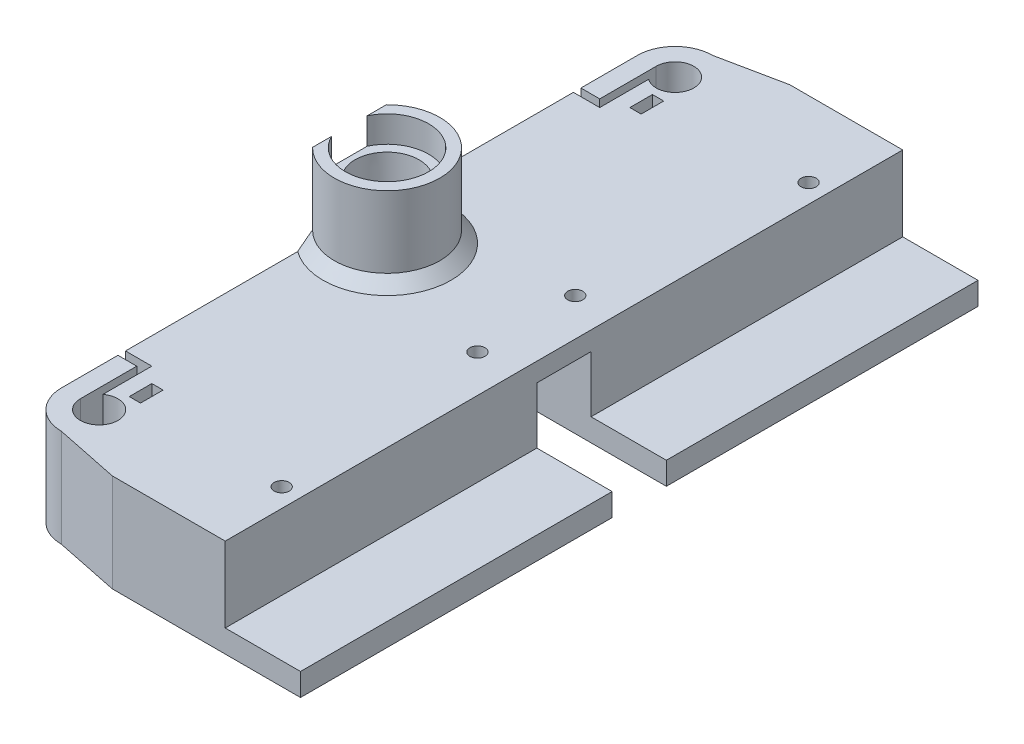
SolidWorks part; units mm, degrees
ref_plane "Płaszczyzna przednia" through (0, 0, 0) normal (0, 0, 1) x (1, 0, 0)
ref_plane "Płaszczyzna górna" through (0, 0, 0) normal (0, 1, 0) x (1, 0, 0)
ref_plane "Płaszczyzna prawa" through (0, 0, 0) normal (1, 0, 0) x (0, 0, -1)
sketch "Szkic1" plane through (0, 0, 0) normal (0, 0, 1) x (1, 0, 0)
  line L0 (10, -10) -> (10, -16)
  line L1 (10, -10) -> (-10, -10)
  line L2 (10, -10) -> (10, 10)
  line L3 (10, 10) -> (-10, 10)
  line L4 (-10, -10) -> (-10, 10)
  line L5 (10, -10) -> (-10, 10) construction
  line L6 (10, 10) -> (-10, -10) construction
  line L7 (10, -16) -> (-40, -16)
  line L8 (-40, -16) -> (-40, 10)
  line L9 (-40, 10) -> (-10, 10)
  point P0 (0, 0)
  dimension "D1" = 20
  dimension "D2" = 50
  dimension "D4" = 6
extrude "Dodanie-wyciągnięcie1" add sketch "Szkic1" along normal blind 180 contours L8 L7 L0 L1 L4 L3 region at (-21.6667, -4.3333, 0)
sketch "Szkic2" plane through (0, 10, 0) normal (0, 1, 0) x (1, 0, 0)
  line L0 (-10, -180) -> (-10, 0) construction
  line L3 (-40, -180) -> (-40, 0) construction
  line L4 (-40, 0) -> (-57, -3.5)
  line L5 (-40, -180) -> (-57, -176.5)
  line L6 (-67, -166.5) -> (-67, -13.5)
  line L7 (-40, 0) -> (-40, -180)
  circle A0 centre (-57, -13.5) radius 5
  circle A1 centre (-57, -166.5) radius 5
  circle A2 centre (-57, -13.5) radius 10
  circle A3 centre (-57, -166.5) radius 10
  circle A4 centre (-57, -90) radius 4
  point P14 (-40, -90)
  line M2 (-40, 0) -> (-40, -180)
  dimension "D1" = 47
  dimension "D2" = 10
  dimension "D6" = 8
  dimension "D3" = 153
  dimension "D4" = 76.5
  dimension "D5" = 5
extrude "Dodanie-wyciągnięcie2" add sketch "Szkic2" against normal blind 26 contours A2 A0 | A3 L5 L4 A2 L6 M2 | A3 A1 region at (-52.6707, 10, 90) region at (-50.1289, 10, 6.6289) region at (-63.8711, 10, 173.3711)
sketch "Szkic3" plane through (0, 10, 0) normal (0, 1, 0) x (1, 0, 0)
  line L0 (-62, -13.5) -> (-62, -28.5)
  line L1 (-62, -28.5) -> (-67, -28.5)
  line L2 (-67, -166.5) -> (-67, -13.5) construction
  line L3 (-67, -30.5) -> (-60, -30.5)
  line L4 (-60, -30.5) -> (-60, -17.5)
  line L5 (-67, -28.5) -> (-67, -30.5)
  circle A0 centre (-57, -13.5) radius 5 construction
  circle A1 centre (-57, -13.5) radius 5
  line M8 (-67, -13.5) -> (-67, -166.5)
  circle M13 centre (-57, -13.5) radius 5
  dimension "D3" = 10
  dimension "D1" = 2
  dimension "D2" = 2
  dimension "D4" = 15
extrude "Wytnij-wyciągnięcie1" cut sketch "Szkic3" against normal blind 26 contours L3 L4 L0 L1 M13 M8 region at (-61.9381, 10, 24.9644)
sketch "Szkic4" plane through (-67, 0, 0) normal (-1, 0, 0) x (0, 0, 1)
  line L0 (28.5, -16) -> (28.5, 10) construction
  line L1 (28.5, 10) -> (13.5, 10) construction
  circle A0 centre (23.5, 3) radius 1.75
  circle A1 centre (23.5, -9) radius 1.75
  dimension "D1" = 3.5
  dimension "D2" = 12
  dimension "D3" = 5
  dimension "D4" = 7
extrude "Wytnij-wyciągnięcie2" cut sketch "Szkic4" against normal blind 11
sketch "Szkic5" plane through (-67, 0, 0) normal (-1, 0, 0) x (0, 0, 1)
  line L0 (20.5, 4.7321) -> (20.5, 10)
  line L1 (23.5, 6.4641) -> (20.5, 4.7321)
  line L2 (20.5, 4.7321) -> (20.5, 1.2679)
  line L3 (20.5, 1.2679) -> (23.5, -0.4641)
  line L4 (23.5, -0.4641) -> (26.5, 1.2679)
  line L5 (26.5, 1.2679) -> (26.5, 4.7321)
  line L6 (26.5, 4.7321) -> (23.5, 6.4641)
  line L7 (23.5, -5.5359) -> (20.5, -7.2679)
  line L8 (20.5, -7.2679) -> (20.5, -10.7321)
  line L9 (20.5, -10.7321) -> (23.5, -12.4641)
  line L10 (23.5, -12.4641) -> (26.5, -10.7321)
  line L11 (26.5, -10.7321) -> (26.5, -7.2679)
  line L12 (26.5, -7.2679) -> (23.5, -5.5359)
  line L13 (28.5, 10) -> (13.5, 10) construction
  line L14 (20.5, 10) -> (26.5, 10)
  line L15 (26.5, 10) -> (26.5, 4.7321)
  line L16 (26.5, -10.7321) -> (26.5, -16)
  line L17 (28.5, -16) -> (13.5, -16) construction
  line L18 (26.5, -16) -> (20.5, -16)
  line L19 (20.5, -16) -> (20.5, -10.7321)
  circle A0 centre (23.5, 3) radius 3 construction
  circle A1 centre (23.5, -9) radius 3 construction
  circle M3 centre (23.5, 3) radius 1.75
  circle M4 centre (23.5, -9) radius 1.75
  line M5 (13.5, -16) -> (28.5, -16)
  line M7 (28.5, 10) -> (13.5, 10)
  dimension "D1" = 6
extrude "Wytnij-wyciągnięcie3" cut sketch "Szkic5" against normal blind 3 from offset 11 contours L5 L6 L1 L2 L3 L4 M3 | L15 L0 L1 L6 M7 | L11 L12 L7 L8 L9 L10 M4 | L19 L16 L10 L9 M5 | M4 | M3 region at (-67, 7.7706, 23.5) region at (-67, 5.5187, 22.0458) region at (-67, -6.4813, 24.9542) region at (-67, -13.7706, 23.5) region at (-67, 3, 23.5) region at (-67, -9, 23.5) offset against normal yes
sketch "Szkic6" plane through (0, -16, 0) normal (0, -1, 0) x (1, 0, 0)
  line L0 (-57, 8.5) -> (-57, 18.5)
  arc A0 (-62, 13.5) -> (-60, 17.5) centre (-57, 13.5) ccw construction
  arc A1 (-62, 13.5) -> (-60, 17.5) centre (-57, 13.5) ccw
  arc M13 (-60, 17.5) -> (-62, 13.5) centre (-57, 13.5) cw
extrude "Dodanie-wyciągnięcie3" add sketch "Szkic6" against normal blind 2 contours L0 M13 region at (-54.8779, -16, 13.5)
ref_plane "Płaszczyzna1" through (0, 0, 90) normal (0, 0, 1) x (1, 0, 0)
mirror "Lustro1" about plane through (0, 0, 90) normal (0, 0, 1) of "Dodanie-wyciągnięcie3", "Wytnij-wyciągnięcie3", "Wytnij-wyciągnięcie2", "Wytnij-wyciągnięcie1"
sketch "Szkic7" plane through (0, -16, 0) normal (0, -1, 0) x (1, 0, 0)
  line L0 (-63, 94.2) -> (-63, 85.8)
  line L1 (-60, 97.2) -> (-55.2, 97.2)
  line L2 (-60, 82.8) -> (-55.2, 82.8)
  line L3 (-48.2, 97.2) -> (11.5715, 97.2)
  line L4 (11.5715, 97.2) -> (11.5715, 82.8)
  line L5 (11.5715, 82.8) -> (-48.2, 82.8)
  circle A0 centre (-57, 90) radius 4 construction
  circle A1 centre (-57, 90) radius 4
  arc A2 (-63, 85.8) -> (-60, 82.8) centre (-60, 85.8) ccw
  arc A3 (-63, 94.2) -> (-60, 97.2) centre (-60, 94.2) cw
  arc A5 (-48.2, 97.2) -> (-55.2, 97.2) centre (-51.7, 97.2) ccw
  arc A7 (-55.2, 82.8) -> (-48.2, 82.8) centre (-51.7, 82.8) ccw
  point P2 (-51.7, 83.4828)
  point P16 (-63, 90)
  point P17 (-51.7, 83)
  point P21 (-48.2, 83)
  point P22 (-57, 90)
  circle M6 centre (-57, 90) radius 4
  dimension "D2" = 3
  dimension "D3" = 11.3
  dimension "D4" = 3.5
  dimension "D1" = 6
  dimension "D5" = 14.4
extrude "Wytnij-wyciągnięcie5" cut sketch "Szkic7" against normal blind 21 contours M6 | L2 A7 L5 L4 L3 A5 L1 A3 L0 A2 M6 region at (-25.0395, -16, 90) region at (-57, -16, 90)
sketch "Szkic8" plane through (0, 5, 0) normal (0, -1, 0) x (1, 0, 0)
  line L1 (-48.2, 94.5) -> (-35.2, 94.5)
  line L2 (-48.2, 94.5) -> (-48.2, 85.5)
  line L3 (-48.2, 85.5) -> (-35.2, 85.5)
  line L4 (-35.2, 94.5) -> (-35.2, 85.5)
  circle A0 centre (-57, 90) radius 4 construction
  circle A1 centre (-57, 90) radius 4
  arc A2 (-55.2, 82.8) -> (-48.2, 82.8) centre (-51.7, 82.8) ccw construction
  arc A3 (-48.2, 97.2) -> (-55.2, 97.2) centre (-51.7, 97.2) ccw construction
  arc A4 (-55.2, 82.8) -> (-48.2, 82.8) centre (-51.7, 82.8) ccw
  arc A5 (-48.2, 97.2) -> (-55.2, 97.2) centre (-51.7, 97.2) ccw
  circle A6 centre (-51.7, 97.2) radius 2
  circle A7 centre (-51.7, 82.8) radius 2
  point P7 (-48.2, 90)
  dimension "D4" = 4
  dimension "D1" = 9
  dimension "D2" = 13
  dimension "D3" = 8.8
extrude "Wytnij-wyciągnięcie6" cut sketch "Szkic8" against normal blind 4 contours L4 L1 L2 L3 | A6 | A7 region at (-41.7, 5, 90) region at (-51.7, 5, 97.2) region at (-51.7, 5, 82.8)
sketch "Szkic9" plane through (0, 10, 0) normal (0, 1, 0) x (1, 0, 0)
  circle A0 centre (-57, -90) radius 14
  circle A1 centre (-57, -90) radius 4 construction
  circle A2 centre (-57, -90) radius 4
extrude "Dodanie-wyciągnięcie4" add sketch "Szkic9" along normal blind 22
sketch "Szkic10" plane through (0, 32, 0) normal (0, 1, 0) x (1, 0, 0)
  circle A0 centre (-57, -90) radius 4 construction
  circle A1 centre (-57, -90) radius 4
  circle A2 centre (-57, -90) radius 11.05
  dimension "D1" = 22.1
extrude "Wytnij-wyciągnięcie7" cut sketch "Szkic10" against normal blind 7
sketch "Szkic11" plane through (0, 25, 0) normal (0, 1, 0) x (1, 0, 0)
  circle A0 centre (-57, -90) radius 8
  circle A1 centre (-57, -90) radius 11.05
  circle A2 centre (-57, -90) radius 11.05
  circle M2 centre (-57, -90) radius 4
  dimension "D2" = 16
  dimension "D1" = 0
extrude "Wytnij-wyciągnięcie8" cut sketch "Szkic11" against normal blind 15 contours A0 M2 region at (-64.7737, 25, 90)
chamfer "Sfazowanie1" distance 0.5 distance2 12 1 edges at (-57, 25, 98) first distance on face at (-57, 25, 98)
sketch "Szkic12" plane through (0, 10, 0) normal (0, 1, 0) x (1, 0, 0)
  line L1 (-67, -99.798) -> (-67, -80.202)
  line L2 (-67, -99.798) -> (-67, -80.202)
  arc A1 (-67, -80.202) -> (-67, -99.798) centre (-57, -90) ccw
  arc A2 (-67, -80.202) -> (-67, -99.798) centre (-57, -90) ccw
  dimension "D1" = 0
extrude "Wytnij-wyciągnięcie9" cut sketch "Szkic12" along normal blind 22
sketch "Szkic13" plane through (0, -16, 0) normal (0, -1, 0) x (1, 0, 0)
  line L0 (10, 82.8) -> (-48.2, 82.8) construction
  line L1 (-60, 104.2) -> (-30, 104.2)
  line L2 (-65, 99.2) -> (-65, 80.8)
  line L3 (-60, 75.8) -> (-30, 75.8)
  line L4 (-25, 99.2) -> (-25, 80.8)
  arc A0 (-65, 80.8) -> (-60, 75.8) centre (-60, 80.8) ccw
  arc A1 (-30, 75.8) -> (-25, 80.8) centre (-30, 80.8) ccw
  arc A2 (-30, 104.2) -> (-25, 99.2) centre (-30, 99.2) cw
  arc A3 (-60, 104.2) -> (-65, 99.2) centre (-60, 99.2) ccw
  circle A4 centre (-57, 90) radius 4 construction
  circle A5 centre (-57, 90) radius 4
  point P6 (-65, 75.8)
  point P11 (-25, 104.2)
  point P14 (-65, 104.2)
  point P18 (-65, 90)
  dimension "D3" = 5
  dimension "D1" = 7
  dimension "D2" = 40
  dimension "D4" = 8
extrude "Wytnij-wyciągnięcie10" cut sketch "Szkic13" against normal blind 3
sketch "Szkic14" plane through (0, -13, 0) normal (0, -1, 0) x (1, 0, 0)
  line L0 (-30, 104.2) -> (-60, 104.2) construction
  line L1 (-65, 99.2) -> (-65, 80.8) construction
  line L2 (-60, 75.8) -> (-30, 75.8) construction
  line L3 (-25, 97.2) -> (-25, 99.2) construction
  circle A0 centre (-60, 101.2) radius 2
  circle A1 centre (-30, 101.2) radius 2
  circle A2 centre (-30, 78.8) radius 2
  circle A3 centre (-60, 78.8) radius 2
  point P12 (0, 0)
  point P13 (0, 0)
  point P14 (0, 0)
  point P15 (0, 0)
  point P20 (-60, 78.8)
  dimension "D1" = 3
  dimension "D3" = 4
  dimension "D4" = 3
  dimension "D2" = 5
  dimension "D5" = 5
extrude "Wytnij-wyciągnięcie11" cut sketch "Szkic14" against normal blind 6
sketch "Szkic15" plane through (0, 10, 0) normal (0, 1, 0) x (1, 0, 0)
  line L0 (-10, -180) -> (-10, 0) construction
  line L1 (-40, -180) -> (-10, -180) construction
  line L2 (-40, 0) -> (-10, 0) construction
  circle A0 centre (-15, -160) radius 2
  circle A1 centre (-20, -103) radius 2
  circle A2 centre (-15, -20) radius 2
  circle A3 centre (-20, -77) radius 2
  point P6 (0, 0)
  point P12 (-10, -90)
  dimension "D1" = 4
  dimension "D6" = 26
  dimension "D2" = 5
  dimension "D3" = 10
  dimension "D4" = 20
  dimension "D5" = 20
  dimension "D7" = 13
extrude "Wytnij-wyciągnięcie12" cut sketch "Szkic15" against normal blind 6
chamfer "Sfazowanie2" distance 3 angle 45 1 edges at (-43, 10, 90)
